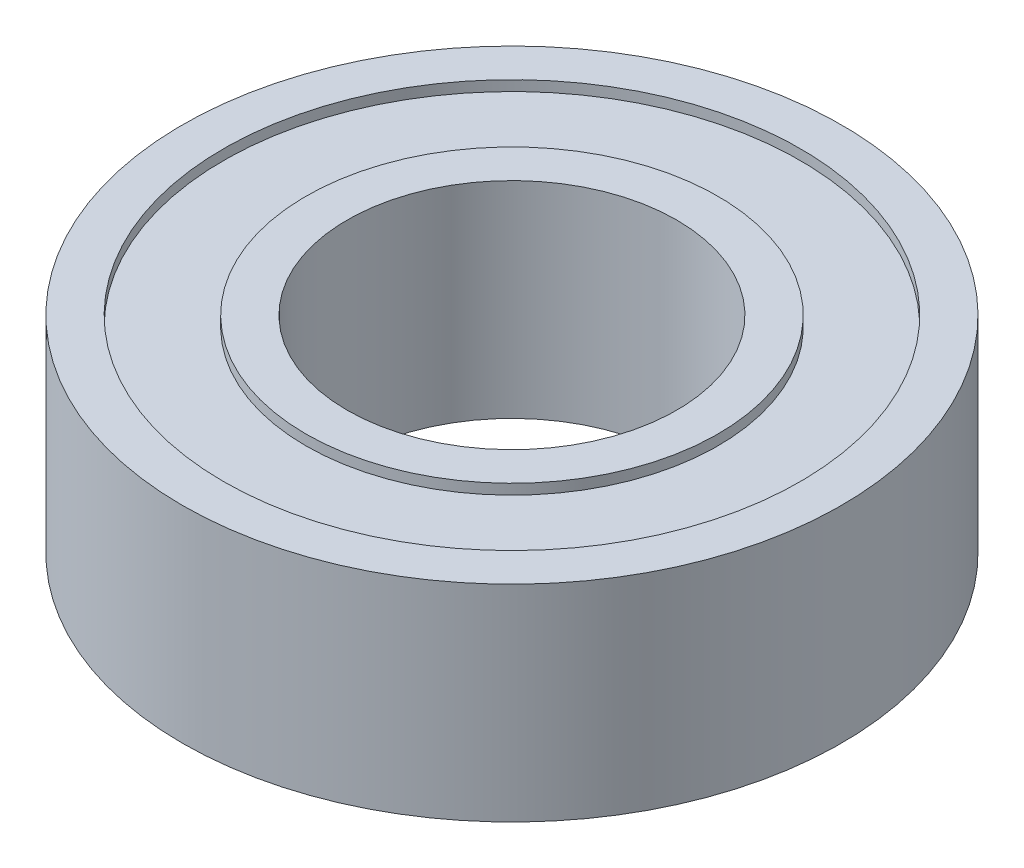
SolidWorks part; units mm, degrees
ref_plane "Front Plane" through (0, 0, 0) normal (0, 0, 1) x (1, 0, 0)
ref_plane "Top Plane" through (0, 0, 0) normal (0, 1, 0) x (1, 0, 0)
ref_plane "Right Plane" through (0, 0, 0) normal (1, 0, 0) x (0, 0, -1)
sketch "Sketch1" plane through (0, 0, 0) normal (0, 1, 0) x (1, 0, 0)
  circle A0 centre (0, 0) radius 4
  circle A1 centre (0, 0) radius 8
  circle A2 centre (0, 0) radius 5
  circle A3 centre (0, 0) radius 7
  dimension "D1" = 8
  dimension "D2" = 16
  dimension "D3" = 1
  dimension "D4" = 1
extrude "Boss-Extrude1" add sketch "Sketch1" along normal blind 2.5 and the other way blind 2.5 contours A1 A3 | A2 A0 region at (-7.7737, 0, 0) region at (-4.8586, 0, 0)
sketch "Sketch2" plane through (0, 0, 0) normal (0, 1, 0) x (1, 0, 0)
  circle A0 centre (0, 0) radius 7
  circle A1 centre (0, 0) radius 5
  dimension "D1" = 14
  dimension "D2" = 10
extrude "Boss-Extrude2" add sketch "Sketch2" along normal blind 2.25 and the other way blind 2.25 separate body
